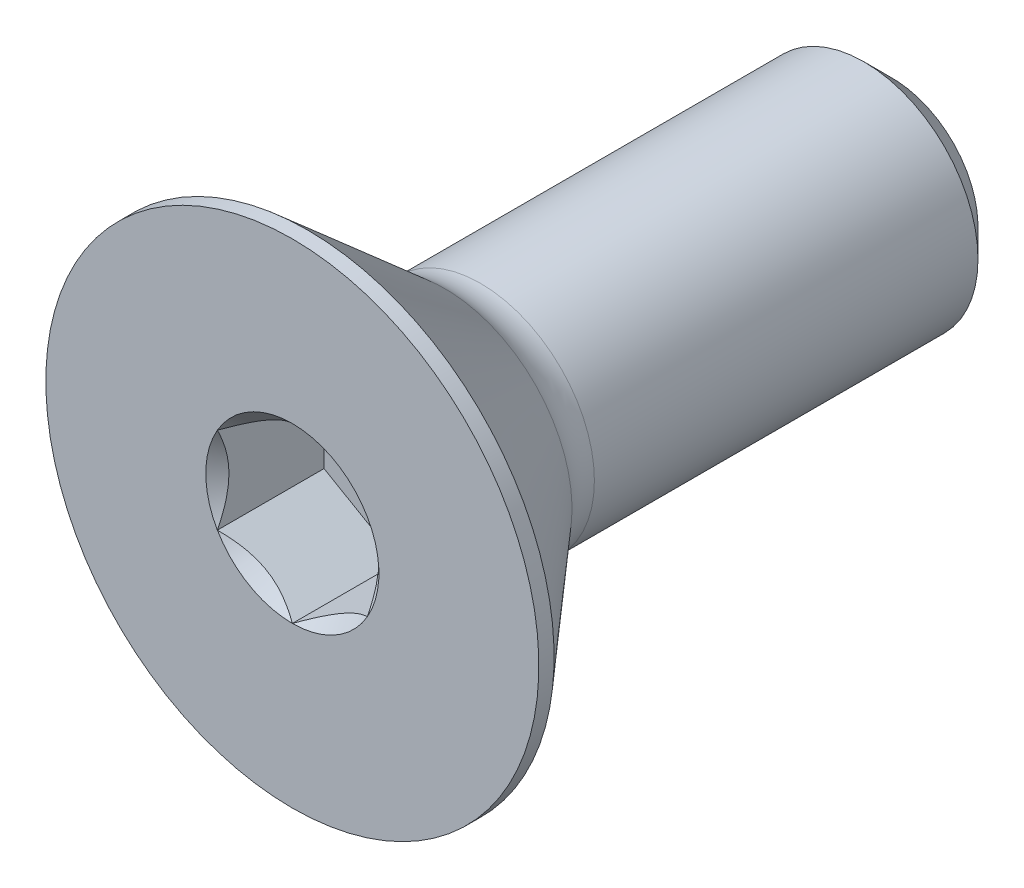
SolidWorks part; units mm, degrees
material "AISI 304"
ref_plane "Front" through (0, 0, 0) normal (0, 0, 1) x (1, 0, 0)
ref_plane "Top" through (0, 0, 0) normal (0, 1, 0) x (1, 0, 0)
ref_plane "Right" through (0, 0, 0) normal (1, 0, 0) x (0, 0, -1)
sketch "Sketch1" plane through (0, 0, 0) normal (1, 0, 0) x (0, 0, -1)
  line L0 (0, 5.2197) -> (0.3226, 5.2197) construction
  line L1 (0.3226, 5.2197) -> (3.2258, 2.696) construction
  line L2 (0, 2.413) -> (12.7, 2.413)
  line L3 (12.7, 2.413) -> (12.7, 0)
  line L4 (12.7, 0) -> (0, 0)
  line L5 (0, 0) -> (0, 5.2197) construction
  line L6 (0, 5.2197) -> (0, -5.2197) construction
  line L7 (12.7, 2.413) -> (12.7, -2.413) construction
  line L8 (0, -5.2197) -> (0.3226, -5.2197) construction
  line L9 (0.3226, -5.2197) -> (3.2258, -2.696) construction
  line L11 (0, 2.413) -> (0, 0)
  line L12 (3.9826, 2.413) -> (3.9826, 0) construction
  arc A1 (3.2258, 2.696) -> (3.9826, 2.413) centre (3.9826, 3.5666) ccw construction
  dimension "D1" = 0.3226
revolve "Revolve1" add sketch "Sketch1" angle 360 mid plane about L4
sketch "Sketch3" plane through (0, 0, -12.7) normal (0, 0, -1) x (-1, 0, 0)
  circle A0 centre (0, 0) radius 2.413
curve "Helix/Spiral1" pitch 0.7937 height 12.7 turns 16
sketch "Sketch2" plane through (0, 0, 0) normal (1, 0, 0) x (0, 0, -1)
  line L0 (12.7, 2.413) -> (13.3945, 2.413)
  line L1 (13.3945, 2.413) -> (13.0969, 1.8974)
  line L2 (13.0969, 1.8974) -> (12.9977, 1.8974)
  line L3 (12.9977, 1.8974) -> (12.7, 2.413)
  line L4 (12.8488, 2.1552) -> (13.2457, 2.1552) construction
  dimension "D1" = 60
  dimension "D2" = 0.0992
  dimension "D3" = 0.3969
chamfer "Chamfer1" distance 0.5953 angle 45 1 edges at (0, 2.413, -12.7)
sweep "Cut-Sweep1" [suppressed] cut profiles "Sketch2" path "Helix/Spiral1"
sketch "Sketch7" plane through (0, 0, 0) normal (1, 0, 0) x (0, 0, -1)
  line L0 (0, 5.2197) -> (0.3226, 5.2197) construction
  line L1 (0.3226, 5.2197) -> (3.2258, 2.696) construction
  line L2 (0, 5.2197) -> (0.3226, 5.2197)
  line L3 (0.3226, 5.2197) -> (3.2258, 2.696)
  line L4 (3.9826, 2.413) -> (3.9826, 0) construction
  line L5 (3.9826, 2.413) -> (3.9826, 0)
  line L7 (0, 0) -> (0, 5.2197) construction
  line L8 (0, 0) -> (0, 5.2197)
  line L9 (0, 0) -> (3.9826, 0)
  line L10 (5.7417, 0) -> (-5.7417, 0) construction
  arc A0 (3.2258, 2.696) -> (3.9826, 2.413) centre (3.9826, 3.5666) ccw construction
  arc A1 (3.2258, 2.696) -> (3.9826, 2.413) centre (3.9826, 3.5666) ccw
revolve "Revolve2" add sketch "Sketch7" angle 360 mid plane about L9
ref_plane "Plane1" through (0, 0, -3.9826) normal (0, 0, 1) x (1, 0, 0)
sketch "Sketch8" plane through (0, 0, -3.9826) normal (0, 0, 1) x (1, 0, 0)
  circle A0 centre (0, 0) radius 2.413
extrude "Boss-Extrude1" add sketch "Sketch8" against normal through all draft 45
sketch "Sketch11" [suppressed] plane through (0, 0, 0) normal (1, 0, 0) x (0, 0, -1)
  line L0 (4.4996, 0) -> (-4.4996, 0) construction
  line L1 (7.3025, 3.8989) -> (1.7272, 3.8989)
  line L2 (7.3025, 3.8989) -> (7.3025, -3.8989)
  line L3 (7.3025, -3.8989) -> (1.7272, -3.8989)
  line L4 (1.7272, 3.8989) -> (1.7272, -3.8989)
  line L5 (0, 3.8989) -> (0.1727, 3.8989) construction
  line L7 (4.7625, 1.7526) -> (4.7625, 0) construction
  point P4 (1.7272, 0)
  dimension "D1" = 2.54
extrude "Cut-Extrude4" [suppressed] cut sketch "Sketch11" against normal through all and the other way through all
combine bodies "Combine1" operation type add bodies to combine 117 108
sketch "Sketch5" plane through (0, 0, 0) normal (0, 0, 1) x (1, 0, 0)
  line L1 (1.5875, -0.9165) -> (1.5875, 0.9165)
  line L2 (1.5875, 0.9165) -> (0, 1.8331)
  line L3 (0, 1.8331) -> (-1.5875, 0.9165)
  line L4 (-1.5875, 0.9165) -> (-1.5875, -0.9165)
  line L5 (-1.5875, -0.9165) -> (0, -1.8331)
  line L6 (0, -1.8331) -> (1.5875, -0.9165)
  circle A0 centre (0, 0) radius 1.5875 construction
  dimension "Hex" = 3.175
extrude "Cut-Extrude2" cut sketch "Sketch5" against normal blind 2.2581
sketch "Sketch6" plane through (0, 0, 0) normal (0, 0, 1) x (1, 0, 0)
  circle A0 centre (0, 0) radius 1.8331
extrude "Cut-Extrude3" cut sketch "Sketch6" against normal blind 2.2581 draft 45
sketch "Sketch9" [suppressed] plane through (0, 0, -10.1329) normal (0, 0, 1) x (1, 0, 0)
  circle A1 centre (0, 0) radius 7.9375
  circle A2 centre (0, 0) radius 7.9375
  point P0 (0, 7.9375)
  dimension "D1" = 0
extrude "Boss-Extrude2" [suppressed] add sketch "Sketch9" against normal offset from surface (104.1671 mm away) 22.225
sketch "Sketch10" plane through (0, 0, 0) normal (1, 0, 0) x (0, 0, -1)
  line L0 (12.7, 2.413) -> (12.7, -2.413) construction
  point P0 (11.5094, -2.413)
  dimension "D1" = 1.1906
equation "\"D3@Helix/Spiral1\" = \"Lg@Sketch1\""
equation "\"D2@Sketch2\" = \"D4@Helix/Spiral1\" * .125"
equation "\"D3@Sketch2\" = \"D4@Helix/Spiral1\" * .5"
equation "\"D1@Chamfer1\" = \"D4@Helix/Spiral1\" * .75"
equation "\"D1@Cut-Extrude2\" = \"Head Ht@Sketch1\" * .7"
equation "\"D1@Sketch1\" = \"Head Ht@Sketch1\" * .1"
equation "\"D1@Sketch10\" = \"D4@Helix/Spiral1\" * 1.5"
equation "\"D1@Cut-Extrude3\" = \"D1@Cut-Extrude2\""
